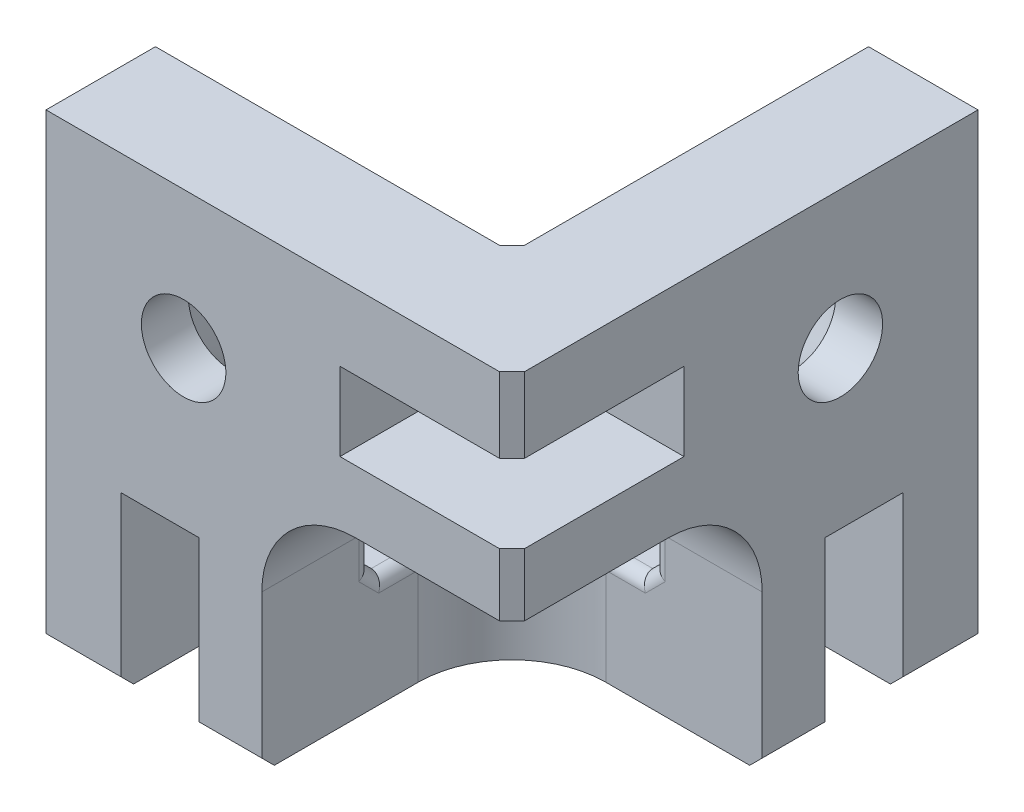
SolidWorks part; units mm, degrees
ref_plane "Plan de face" through (0, 0, 0) normal (0, 0, 1) x (1, 0, 0)
ref_plane "Plan de dessus" through (0, 0, 0) normal (0, 1, 0) x (1, 0, 0)
ref_plane "Plan de droite" through (0, 0, 0) normal (1, 0, 0) x (0, 0, -1)
sketch "Esquisse1" plane through (0, 0, 0) normal (0, 1, 0) x (1, 0, 0)
  line L13 (-8, 8) -> (8, 8)
  line L14 (-8, 8) -> (-8, -8)
  line L15 (-8, -8) -> (8, -8)
  line L16 (8, 8) -> (8, -8)
  line L17 (-8, 8) -> (8, -8) construction
  line L18 (-8, -8) -> (8, 8) construction
  point P0 (0, 0)
  dimension "D1" = 16
extrude "Boss.-Extru.1" add sketch "Esquisse1" along normal blind 16
shell "Coque2" thickness 3.5 removed face at (-8, 8, 0) removed face at (0, 8, -8) removed face at (0, 16, 0)
sketch "Esquisse2" plane through (0, 0, 0) normal (0, -1, 0) x (1, 0, 0)
  line L0 (-8, 8) -> (8, 8) construction
  line L1 (-4.5, 8) -> (-2, 8)
  line L2 (-4.5, 8) -> (-4.5, 2.5)
  line L3 (-4.5, 2.5) -> (-2, 2.5)
  line L4 (-2, 8) -> (-2, 2.5)
  line L5 (8, 8) -> (8, -8) construction
  line L6 (8, -2) -> (2.5, -2)
  line L7 (8, -2) -> (8, -4.5)
  line L8 (8, -4.5) -> (2.5, -4.5)
  line L9 (2.5, -2) -> (2.5, -4.5)
  dimension "D1" = 5.5
  dimension "D2" = 2.5
  dimension "D3" = 10
  dimension "D4" = 10
extrude "Enlèv. mat.-Extru.1" cut sketch "Esquisse2" against normal blind 5.5
sketch "Esquisse3" plane through (0, 0, 8) normal (0, 0, 1) x (1, 0, 0)
  line L0 (8, 16) -> (8, 0) construction
  line L1 (8, 12.5) -> (2.5, 12.5)
  line L2 (8, 12.5) -> (8, 10)
  line L3 (8, 10) -> (2.5, 10)
  line L4 (2.5, 12.5) -> (2.5, 10)
  dimension "D1" = 5.5
  dimension "D2" = 2.5
  dimension "D3" = 10
extrude "Enlèv. mat.-Extru.2" cut sketch "Esquisse3" against normal blind 5.5
sketch "Esquisse7" plane through (0, 0, 0) normal (0, -1, 0) x (1, 0, 0)
  line L0 (-2, 8) -> (8, 8) construction
  line L1 (8, 8) -> (8, -2) construction
  line L2 (3, 0) -> (8, 0)
  line L3 (8, 0) -> (8, 8)
  line L4 (8, 8) -> (0, 8)
  line L5 (0, 8) -> (0, 3)
  arc A0 (0, 3) -> (3, 0) centre (3, 3) ccw
  dimension "D3" = 6
  dimension "D1" = 5
  dimension "D2" = 5
extrude "Enlèv. mat.-Extru.3" cut sketch "Esquisse7" against normal up to surface (3.5 mm away) up to face at (-0.5, 3.5, -0.5)
sketch "Esquisse8" plane through (0, 0, 8) normal (0, 0, 1) x (1, 0, 0)
  line L0 (-2, 0) -> (0, 0) construction
  line L1 (8, 10) -> (8, 3.5) construction
  line L2 (3, 8) -> (8, 8)
  line L3 (8, 8) -> (8, 0)
  line L4 (8, 0) -> (0, 0)
  line L5 (0, 0) -> (0, 5)
  arc A0 (3, 8) -> (0, 5) centre (3, 5) ccw
  dimension "D3" = 6
  dimension "D1" = 5
  dimension "D2" = 5
extrude "Enlèv. mat.-Extru.4" cut sketch "Esquisse8" against normal up to surface (3.5 mm away) up to face at (-0.4615, 8.1154, 4.5)
sketch "Esquisse9" plane through (8, 0, 0) normal (1, 0, 0) x (0, 0, -1)
  line L0 (-8, 10) -> (-8, 8) construction
  line L1 (0, 0) -> (2, 0) construction
  line L2 (-3, 8) -> (-8, 8)
  line L3 (-8, 8) -> (-8, 0)
  line L4 (-8, 0) -> (0, 0)
  line L5 (0, 0) -> (0, 5)
  arc A0 (0, 5) -> (-3, 8) centre (-3, 5) ccw
  dimension "D3" = 6
  dimension "D1" = 5
  dimension "D2" = 5
extrude "Enlèv. mat.-Extru.5" cut sketch "Esquisse9" against normal up to surface (3.5 mm away) up to face at (4.5, 8.1071, -0.1071)
hole_wizard "Fraisage pour vis à tête fraisée M2.51" positions "Esquisse3D1" profile "Esquisse17" countersink size "M2.5" standard "ISO" end condition through all
sketch3d "Esquisse3D1"
  line L0 (4.5, 16, 4.5) -> (4.5, 16, -8) construction
  line L1 (4.5, 16, -8) -> (4.5, 3.5, -8) construction
  line L2 (-8, 3.5, -8) -> (-8, 3.5, 4.5) construction
  line L3 (4.5, 3.5, -8) -> (-8, 3.5, -8) construction
  line L4 (-8, 16, 4.5) -> (4.5, 16, 4.5) construction
  line L5 (-8, 16, 4.5) -> (-8, 3.5, 4.5) construction
  point P0 (4.5, 10.5, -2.5)
  point P2 (-2.5, 10.5, 4.5)
  point P4 (-2.5, 3.5, -2.5)
  dimension "D1" = 5.5
  dimension "D2" = 5.5
  dimension "D3" = 5.5
  dimension "D4" = 5.5
  dimension "D5" = 5.5
  dimension "D6" = 5.5
sketch "Esquisse17" plane through (4.5, 10.5, -2.5) normal (0, 1, 0) x (0, 0, 1)
  line L0 (0, 0) -> (0, 3.5)
  line L1 (0, 3.5) -> (1.35, 3.5)
  line L2 (1.35, 3.5) -> (1.35, 2)
  line L3 (1.35, 2) -> (3.35, 0)
  line L5 (3.35, 0) -> (0, 0)
  line L6 (-1.35, 2) -> (-3.35, 0) construction
  line L11 (0, -6.35) -> (0, 107.95) construction
  dimension "Diamètre du perçage jusqu'au prochain" = 2.7
  dimension "Profondeur du perçage jusqu'au prochain" = 3.5
  dimension "Diamètre du fraisage entrant" = 6.7
  dimension "Angle du fraisage entrant" = 90
sketch "Esquisse10" plane through (0, 16, 0) normal (0, 1, 0) x (1, 0, 0)
  line L0 (4.5, 8) -> (4.5, -4.5)
  line L1 (4.5, -4.5) -> (-8, -4.5)
  line L2 (-8, -4.5) -> (-8, -8)
  line L3 (-8, -8) -> (8, -8)
  line L4 (8, -8) -> (8, 8)
  line L5 (8, 8) -> (4.5, 8)
extrude "Enlèv. mat.-Extru.6" cut sketch "Esquisse10" against normal blind 1.1
sketch "Esquisse11" plane through (0, 0, -8) normal (0, 0, -1) x (-1, 0, 0)
  line L12 (-4.5, 14.9) -> (-8, 14.9)
  line L13 (-8, 14.9) -> (-8, 0)
  line L14 (-8, 0) -> (8, 0)
  line L15 (8, 0) -> (8, 3.5)
  line L16 (8, 3.5) -> (-4.5, 3.5)
  line L17 (-4.5, 3.5) -> (-4.5, 14.9)
  line L18 (-4.5, 14.9) -> (-8, 14.9)
  line L19 (-8, 14.9) -> (-8, 0)
  line L20 (-8, 0) -> (8, 0)
  line L21 (8, 0) -> (8, 3.5)
  line L22 (8, 3.5) -> (-4.5, 3.5)
  line L23 (-4.5, 3.5) -> (-4.5, 14.9)
  dimension "D1" = 0
extrude "Enlèv. mat.-Extru.7" cut sketch "Esquisse11" against normal blind 1.1
sketch "Esquisse13" plane through (-8, 0, 0) normal (-1, 0, 0) x (0, 0, 1)
  line L12 (-6.9, 3.5) -> (-6.9, 0)
  line L13 (-6.9, 0) -> (8, 0)
  line L14 (8, 0) -> (8, 14.9)
  line L15 (8, 14.9) -> (4.5, 14.9)
  line L16 (4.5, 14.9) -> (4.5, 3.5)
  line L17 (4.5, 3.5) -> (-6.9, 3.5)
  line L18 (-6.9, 3.5) -> (-6.9, 0)
  line L19 (-6.9, 0) -> (8, 0)
  line L20 (8, 0) -> (8, 14.9)
  line L21 (8, 14.9) -> (4.5, 14.9)
  line L22 (4.5, 14.9) -> (4.5, 3.5)
  line L23 (4.5, 3.5) -> (-6.9, 3.5)
  dimension "D1" = 0
extrude "Enlèv. mat.-Extru.8" cut sketch "Esquisse13" against normal blind 1.1
chamfer "Chanfrein1" distance 0.4 angle 45 12 edges at (4.5, 13.7, 4.5) (-5.7, 3.5, 4.5) (4.5, 9, 4.5) (-1, 3.5, 4.5) (4.5, 3.5, -1) (4.5, 3.5, -5.7) (8, 0, -5.7) (-5.7, 0, 8) (8, 13.7, 8) (8, 0, -1) (8, 9, 8) (-1, 0, 8)
fillet "Congé1" radius 0.4 12 edges at (0.8787, 3.5, 0.8787) (0.8787, 7.1213, 4.5) (4.5, 7.1213, 0.8787) (4.5, 4.45, 0) (4.5, 8, 3.55) (3.55, 8, 4.5) (0, 4.45, 4.5) (0, 3.5, 3.55) (3.55, 3.5, 0) (4.3, 8, 4.3) (0, 3.7, 4.3) (4.3, 3.7, 0)
